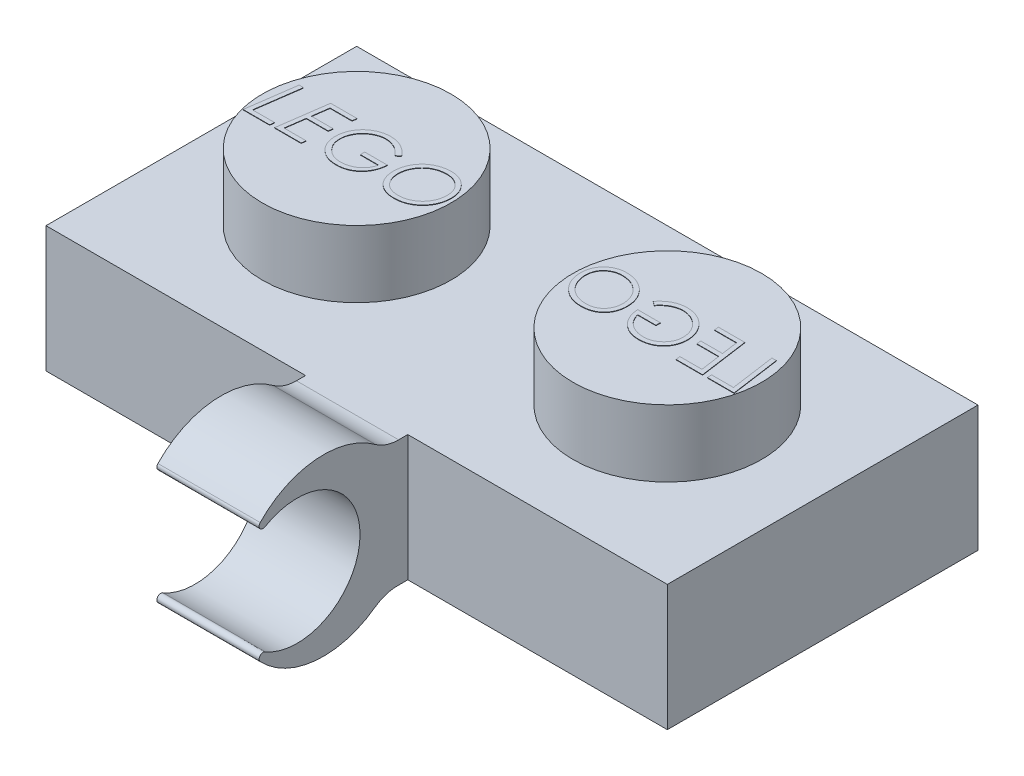
SolidWorks part; units mm, degrees
ref_plane "Front Plane" through (0, 0, 0) normal (0, 0, 1) x (1, 0, 0)
ref_plane "Top Plane" through (0, 0, 0) normal (0, 1, 0) x (1, 0, 0)
ref_plane "Right Plane" through (0, 0, 0) normal (1, 0, 0) x (0, 0, -1)
sketch "Sketch1" plane through (0, 0, 0) normal (0, 1, 0) x (1, 0, 0)
  line L0 (0, 0) -> (7.9, 0)
  line L1 (7.9, 0) -> (7.9, 7.9)
  line L2 (0, 0) -> (0, 7.9)
  line L3 (0, 7.9) -> (7.9, 7.9)
  dimension "D1" = 7.9
  dimension "D2" = 7.9
  dimension "D3" = 7.9
extrude "Boss-Extrude1" add sketch "Sketch1" along normal blind 3.2
sketch "Sketch2" plane through (0, 3.2, 0) normal (0, 1, 0) x (1, 0, 0)
  line L0 (0, 7.9) -> (7.9, 0) construction
  circle A0 centre (3.95, 3.95) radius 2.4
extrude "Boss-Extrude2" add sketch "Sketch2" along normal blind 1.7
sketch "Sketch3" plane through (0, 4.9, 0) normal (0, 1, 0) x (1, 0, 0)
  line L0 (1.625, 3.3549) -> (6.275, 3.3549) construction
  circle A0 centre (3.95, 3.95) radius 2.4 construction
  circle A1 centre (3.95, 3.95) radius 2.4 construction
  text T0 "<i>LEGO</i>" font "Century Gothic" height 1.25
extrude "Boss-Extrude4" add sketch "Sketch3" along normal blind 0.01
sketch "Sketch4" plane through (0, 0, 0) normal (0, -1, 0) x (1, 0, 0)
  line L0 (7.9, -7.9) -> (0, -7.9) construction
  line L1 (7.3, -7.3) -> (0.6204, -7.3)
  line L2 (7.3, -7.3) -> (7.3, -0.6204)
  line L3 (7.3, -0.6204) -> (0.6204, -0.6204)
  line L4 (0.6204, -7.3) -> (0.6204, -0.6204)
  line L5 (7.9, 0) -> (7.9, -7.9) construction
  dimension "D1" = 0.6
  dimension "D2" = 0.6
extrude "Cut-Extrude1" cut sketch "Sketch4" against normal blind 2.01 contours L2 L1 L4 L3
sketch "Sketch5" plane through (0, 3.2, 0) normal (0, 1, 0) x (1, 0, 0)
  line L1 (1.4581, 1.5578) -> (6.3695, 1.5578)
  line L2 (1.4581, 1.5578) -> (1.4581, 6.3652)
  line L3 (1.4581, 6.3652) -> (6.3695, 6.3652)
  line L4 (6.3695, 1.5578) -> (6.3695, 6.3652)
  circle A1 centre (6.3695, 6.3652) radius 1.0161
  circle A2 centre (6.3695, 1.5578) radius 1.0061
  circle A3 centre (1.4581, 1.5578) radius 1.0219
  circle A4 centre (1.4581, 6.3652) radius 1.0411
  circle M5 centre (3.95, 3.95) radius 2.4
extrude "Boss-Extrude5" add sketch "Sketch5" against normal blind 2.01 contours L1 A2 L4 | L2 A3 L1 | L1 A3 L2 | L4 A2 L1 M5 | L4 A1 L3 | L3 A1 L4 | L2 A4 L3 | L3 A4 L2 region at (1.8919, 3.2, -1.9915) region at (1.3136, 3.2, -1.4132) region at (1.3108, 3.2, -6.5125) region at (1.9, 3.2, -5.9234) region at (5.9427, 3.2, -1.9847) region at (6.5119, 3.2, -1.4155) region at (6.5133, 3.2, -6.509) region at (5.9383, 3.2, -5.934)
mirror "Mirror1" about plane through (7.9, 3.2, 0) normal (-1, 0, 0) of bodies 106
ref_plane "Plane1" through (7.9, 0, 0) normal (-1, 0, 0) x (0, 0, 1)
sketch "Sketch6" plane through (7.9, 0, 0) normal (-1, 0, 0) x (0, 0, 1)
  line L2 (0, 3.2) -> (0.611, 3.2)
  line L3 (0, 3.2) -> (0, 0)
  line L4 (0, 0) -> (0.611, 0)
  line L5 (0.611, 3.2) -> (0.611, 0)
  circle A0 centre (2.8141, 1.6073) radius 1.6
  circle A1 centre (2.1442, 1.6073) radius 2.2213
  dimension "D1" = 3.2
extrude "Boss-Extrude7" add sketch "Sketch6" against normal blind 1.3 and the other way blind 1.3 contours A0 A1 L5 | A1 L5 L2 L3 | L5 A1 L3 | A1 L3 L4 region at (7.9, 2.9021, 0.1799) region at (7.9, 3.7098, 2.6558) region at (7.9, 1.6072, 0.3465) region at (7.9, 0.3017, 0.1843)
fillet "Fillet2" radius 0.1 2 edges at (7.9, 0.904, 4.2513) (7.9, 2.3106, 4.2513)
fillet "Fillet5" radius 1 2 edges at (7.9, 0, 0.611) (7.9, 3.2, 0.5958)
